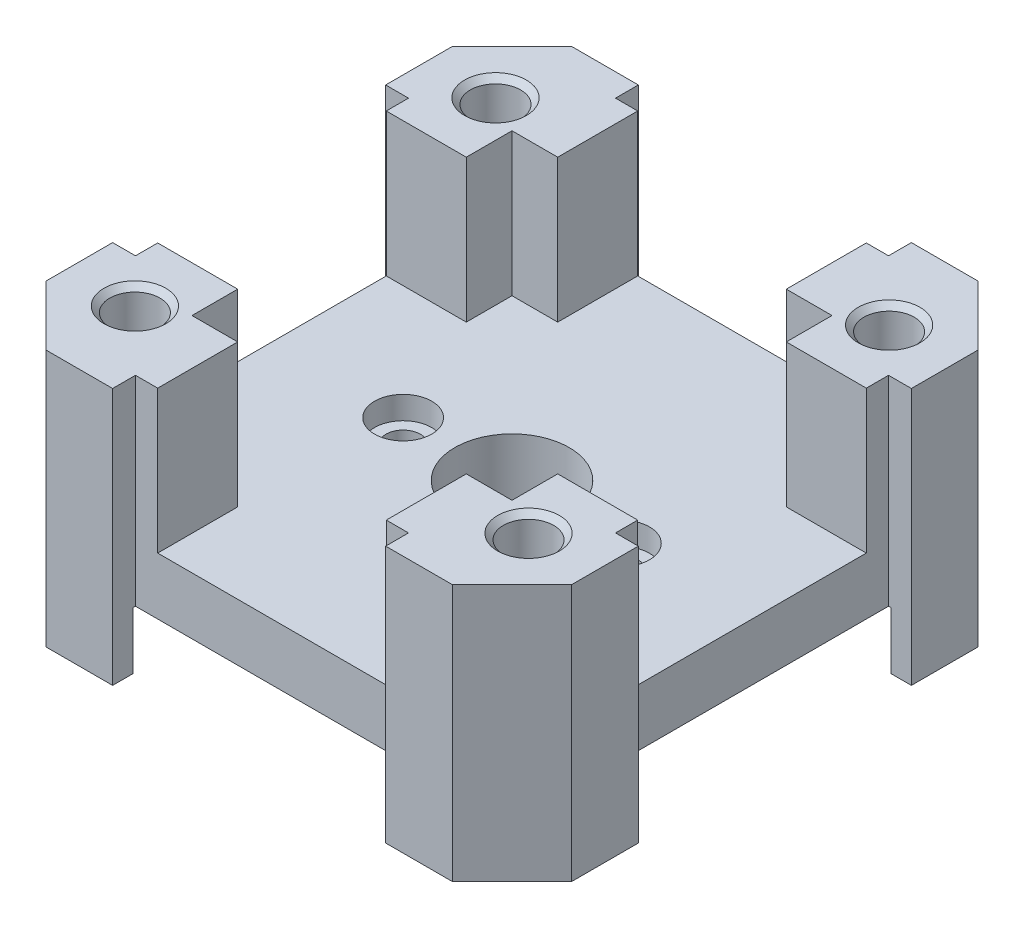
SolidWorks part; units mm, degrees
ref_plane "Front Plane" through (0, 0, 0) normal (0, 0, 1) x (1, 0, 0)
ref_plane "Top Plane" through (0, 0, 0) normal (0, 1, 0) x (1, 0, 0)
ref_plane "Right Plane" through (0, 0, 0) normal (1, 0, 0) x (0, 0, -1)
sketch "Sketch1" plane through (0, 0, 0) normal (0, 1, 0) x (1, 0, 0)
  line L0 (21, 42) -> (21, 0) construction
  line L5 (4.055, 0) -> (37.945, 0)
  line L6 (0, 4.055) -> (0, 37.945)
  line L7 (4.055, 42) -> (37.945, 42)
  line L8 (42, 4.055) -> (42, 37.945)
  line L9 (42, 21) -> (0, 21) construction
  line L10 (0, 37.945) -> (4.055, 42)
  line L11 (37.945, 42) -> (42, 37.945)
  line L12 (37.945, 0) -> (42, 4.055)
  line L13 (4.055, 0) -> (0, 4.055)
  circle A2 centre (11.475, 21) radius 1.5
  circle A3 centre (30.525, 21) radius 1.5
  circle A4 centre (21, 21) radius 5
  point P0 (0, 0)
  point P1 (0, 0)
  point P2 (42, 42)
  point P3 (0, 42)
  point P4 (42, 0)
  dimension "D4" = 3
  dimension "D5" = 3
  dimension "D13" = 10
  dimension "D1" = 42
  dimension "D2" = 42
  dimension "D3" = 19.05
  dimension "D10" = 33.89
  dimension "D9" = 33.89
  dimension "D14" = 16.945
  dimension "D6" = 21
  dimension "D7" = 21
  dimension "D8" = 9.525
  dimension "D11" = 33.89
  dimension "D12" = 33.89
  dimension "D15" = 16.945
  dimension "D16" = 16.945
  dimension "D17" = 16.945
extrude "Boss-Extrude1" add sketch "Sketch1" along normal blind 5
sketch "Sketch2" plane through (0, 5, 0) normal (0, 1, 0) x (1, 0, 0)
  line L45 (35, 7) -> (35, 35)
  line L47 (7, 7) -> (35, 7)
  line L49 (7, 35) -> (7, 7)
  line L51 (35, 35) -> (7, 35)
  line L53 (35, 7) -> (35, 35)
  line L55 (7, 7) -> (35, 7)
  line L57 (7, 35) -> (7, 7)
  line L59 (35, 35) -> (7, 35)
  line M14 (4.055, 42) -> (0, 37.945)
  line M15 (0, 37.945) -> (0, 4.055)
  line M16 (0, 4.055) -> (4.055, 0)
  line M17 (4.055, 0) -> (37.945, 0)
  line M18 (37.945, 0) -> (42, 4.055)
  line M19 (42, 4.055) -> (42, 37.945)
  line M20 (42, 37.945) -> (37.945, 42)
  line M21 (37.945, 42) -> (4.055, 42)
  dimension "D1" = 7
extrude "Boss-Extrude2" add sketch "Sketch2" along normal blind 12.5 contours L59 L53 L55 L57 M21 M14 M15 M16 M17 M18 M19 M20 region at (21, 5, -41.406)
sketch "Sketch3" plane through (0, 17.5, 0) normal (0, 1, 0) x (1, 0, 0)
  line L0 (4.055, 42) -> (0, 37.945) construction
  line L1 (0, 4.055) -> (4.055, 0) construction
  line L2 (35, 35) -> (7, 35) construction
  line L3 (7, 7) -> (35, 7) construction
  line L4 (7, 35) -> (7, 7) construction
  line L7 (21, 42) -> (21, 0) construction
  line L8 (37.945, 42) -> (4.055, 42) construction
  line L9 (4.055, 0) -> (37.945, 0) construction
  circle A0 centre (3.7797, 36.775) radius 2.2
  circle A7 centre (3.7797, 5.225) radius 2.2
  circle A8 centre (38.2203, 5.225) radius 2.2
  circle A9 centre (38.2203, 36.775) radius 2.2
  dimension "D1" = 4.4
  dimension "D2" = 3.5
  dimension "D3" = 1.775
  dimension "D4" = 3.2203
  dimension "D5" = 4.4
  dimension "D7" = 1.775
  dimension "D6" = 3.5
extrude "Cut-Extrude1" cut sketch "Sketch3" against normal blind 6
sketch "Sketch4" plane through (0, 0, 0) normal (-1, 0, 0) x (0, 0, 1)
  line L0 (-42, 17.5) -> (-42, 0) construction
  line L1 (-31, 28.0785) -> (-11, 28.0785)
  line L2 (-31, 28.0785) -> (-31, 5)
  line L3 (-31, 5) -> (-11, 5)
  line L4 (-11, 28.0785) -> (-11, 5)
  line L5 (-37.945, 0) -> (-4.055, 0) construction
  dimension "D1" = 20
  dimension "D2" = 11
  dimension "D3" = 5
extrude "Cut-Extrude2" cut sketch "Sketch4" against normal through all both and the other way through all
sketch "Sketch5" plane through (0, 0, -42) normal (0, 0, -1) x (-1, 0, 0)
  line L0 (-42, 17.5) -> (-42, 0) construction
  line L1 (-31, 18.3664) -> (-11, 18.3664)
  line L2 (-31, 18.3664) -> (-31, 5)
  line L3 (-31, 5) -> (-11, 5)
  line L4 (-11, 18.3664) -> (-11, 5)
  line L5 (-37.945, 0) -> (-4.055, 0) construction
  dimension "D1" = 20
  dimension "D2" = 11
  dimension "D3" = 5
extrude "Cut-Extrude3" cut sketch "Sketch5" against normal through all both and the other way through all
sketch "Sketch7" plane through (0, 0, 0) normal (0, -1, 0) x (1, 0, 0)
  line L0 (37.945, 0) -> (32.945, 0)
  line L1 (4.055, 0) -> (0, -4.055)
  line L2 (0, -4.055) -> (0, -9.055)
  line L3 (0, -37.945) -> (4.055, -42)
  line L4 (4.055, -42) -> (9.055, -42)
  line L5 (37.945, -42) -> (42, -37.945)
  line L6 (42, -37.945) -> (42, -32.945)
  line L7 (42, -4.055) -> (37.945, 0)
  line L8 (9.055, 2) -> (9.055, 0)
  line L9 (9.055, -42) -> (9.055, -44)
  line L10 (32.945, -44) -> (32.945, -42)
  line L11 (32.945, 0) -> (32.945, 2)
  line L12 (44, -9.055) -> (42, -9.055)
  line L13 (0, -9.055) -> (-2, -9.055)
  line L14 (-2, -32.945) -> (0, -32.945)
  line L15 (42, -32.945) -> (44, -32.945)
  line L16 (-2, -32.945) -> (-2, -38.7734)
  line L17 (-2, -3.2266) -> (-2, -38.7734) construction
  line L18 (9.055, 2) -> (3.2266, 2)
  line L19 (38.7734, 2) -> (3.2266, 2) construction
  line L20 (9.055, 0) -> (4.055, 0)
  line L21 (37.945, 0) -> (4.055, 0) construction
  line L22 (42, -9.055) -> (42, -4.055)
  line L23 (42, -37.945) -> (42, -4.055) construction
  line L24 (44, -9.055) -> (44, -3.2266)
  line L25 (44, -38.7734) -> (44, -3.2266) construction
  line L26 (32.945, -42) -> (37.945, -42)
  line L27 (4.055, -42) -> (37.945, -42) construction
  line L28 (32.945, -44) -> (38.7734, -44)
  line L29 (3.2266, -44) -> (38.7734, -44) construction
  line L31 (0, -32.945) -> (0, -37.945)
  line L32 (0, -4.055) -> (0, -37.945) construction
  line L44 (44, -3.2266) -> (38.7734, 2)
  line L45 (44, -38.7734) -> (44, -3.2266)
  line L46 (38.7734, -44) -> (44, -38.7734)
  line L47 (3.2266, -44) -> (38.7734, -44)
  line L48 (-2, -38.7734) -> (3.2266, -44)
  line L49 (-2, -3.2266) -> (-2, -38.7734)
  line L50 (3.2266, 2) -> (-2, -3.2266)
  line L51 (38.7734, 2) -> (3.2266, 2)
  line L52 (44, -3.2266) -> (38.7734, 2)
  line L53 (44, -38.7734) -> (44, -32.945)
  line L54 (38.7734, -44) -> (44, -38.7734)
  line L55 (3.2266, -44) -> (9.055, -44)
  line L56 (-2, -38.7734) -> (3.2266, -44)
  line L57 (-2, -3.2266) -> (-2, -9.055)
  line L58 (3.2266, 2) -> (-2, -3.2266)
  line L59 (38.7734, 2) -> (32.945, 2)
  dimension "D3" = 5
  dimension "D4" = 5
  dimension "D5" = 5
  dimension "D6" = 5
  dimension "D7" = 5
  dimension "D1" = 2
  dimension "D2" = 2
extrude "Boss-Extrude3" add sketch "Sketch7" along normal blind 5 and the other way up to surface (17.5 mm away) other way up to face at (36.2779, 17.5, -5.7221)
sketch "Sketch8" plane through (0, 5, 0) normal (0, 1, 0) x (1, 0, 0)
  circle A0 centre (11.475, 21) radius 2.5
  circle A1 centre (30.525, 21) radius 2.5
  dimension "D1" = 5
  dimension "D2" = 5
extrude "Cut-Extrude4" cut sketch "Sketch8" against normal blind 2
sketch "Sketch9" plane through (0, -5, 0) normal (0, -1, 0) x (1, 0, 0)
  line L0 (-0.2, -9.055) -> (-0.2, -3.9722)
  line L1 (-2, -9.055) -> (0, -9.055) construction
  line L2 (-0.2, -3.9722) -> (3.9722, 0.2)
  line L3 (3.9722, 0.2) -> (38.0278, 0.2)
  line L4 (38.0278, 0.2) -> (42.2, -3.9722)
  line L5 (42.2, -3.9722) -> (42.2, -38.0278)
  line L6 (42.2, -38.0278) -> (38.0278, -42.2)
  line L7 (38.0278, -42.2) -> (3.9722, -42.2)
  line L8 (3.9722, -42.2) -> (-0.2, -38.0278)
  line L9 (-0.2, -38.0278) -> (-0.2, -9.055)
  line L10 (0, -4.055) -> (4.055, 0) construction
  line L11 (4.055, 0) -> (9.055, 0) construction
  line L12 (0, -9.055) -> (0, -4.055) construction
  line L13 (37.945, 0) -> (42, -4.055) construction
  line L14 (42, -9.055) -> (42, -32.945) construction
  line L15 (42, -37.945) -> (37.945, -42) construction
  line L16 (37.945, -42) -> (32.945, -42) construction
  line L17 (4.055, -42) -> (0, -37.945) construction
  dimension "D1" = 0.2
  dimension "D2" = 0.2
  dimension "D3" = 0.2
  dimension "D4" = 0.2
  dimension "D5" = 0.2
  dimension "D6" = 0.2
  dimension "D7" = 0.2
extrude "Cut-Extrude5" cut sketch "Sketch9" against normal up to surface (5 mm away) up to face at (30.525, 0, -19.5)
fillet "Fillet1" radius 0.5 8 edges at (38.0278, -2.5, -42.2) (42.2, -2.5, -38.0278) (-0.2, -2.5, -38.0278) (3.9722, -2.5, -42.2) (-0.2, -2.5, -3.9722) (3.9722, -2.5, 0.2) (42.2, -2.5, -3.9722) (38.0278, -2.5, 0.2)
chamfer "Chamfer1" distance 0.5 angle 45 4 edges at (3.7797, 17.5, -3.025) (38.2203, 17.5, -7.425) (38.2203, 17.5, -38.975) (3.7797, 17.5, -34.575)
equation "\"offset\"= 0.20"
equation "\"D2@Sketch9\"=\"offset\""
equation "\"D1@Sketch9\"=\"offset\""
equation "\"D3@Sketch9\"=\"offset\""
equation "\"D8@Sketch9\"=\"offset\""
equation "\"D7@Sketch9\"=\"offset\""
equation "\"D6@Sketch9\"=\"offset\""
equation "\"D5@Sketch9\"=\"offset\""
equation "\"D4@Sketch9\"=\"offset\""
